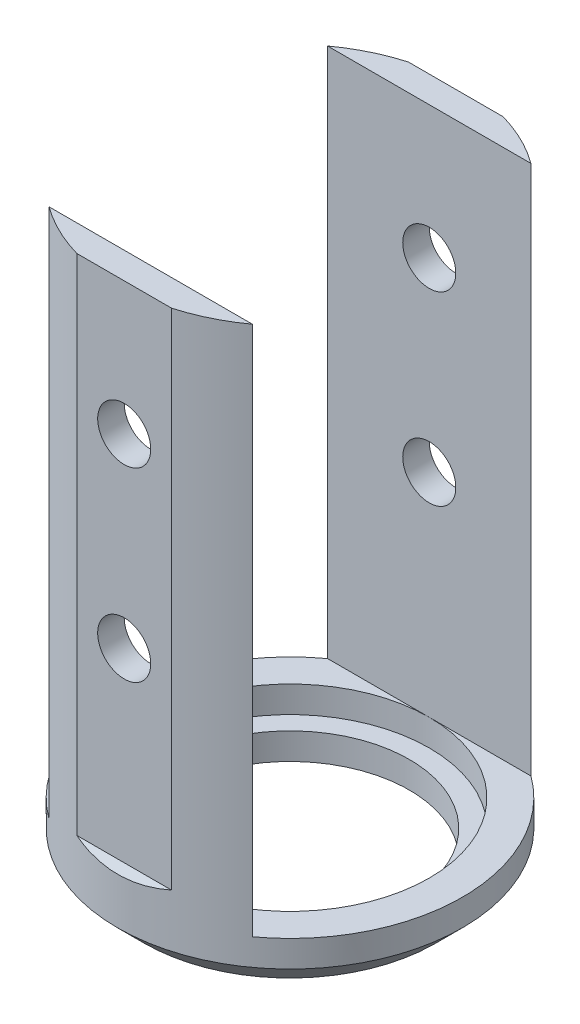
SolidWorks part; units mm, degrees
ref_plane "前视基准面" through (0, 0, 0) normal (0, 0, 1) x (1, 0, 0)
ref_plane "上视基准面" through (0, 0, 0) normal (0, 1, 0) x (1, 0, 0)
ref_plane "右视基准面" through (0, 0, 0) normal (1, 0, 0) x (0, 0, -1)
other "Configuration Table"
sketch "草图1" plane through (0, 0, 0) normal (0, 1, 0) x (1, 0, 0)
  circle A0 centre (0, 0) radius 4.5
  circle A1 centre (0, 0) radius 6.5
  dimension "D1" = 9
  dimension "D2" = 13
extrude "凸台-拉伸1" add sketch "草图1" along normal blind 2
sketch "草图2" plane through (0, 2, 0) normal (0, 1, 0) x (1, 0, 0)
  circle A0 centre (0, 0) radius 5.25
  dimension "D1" = 10.5
extrude "切除-拉伸1" cut sketch "草图2" against normal blind 1
sketch "草图3" plane through (0, 2, 0) normal (0, 1, 0) x (1, 0, 0)
  line L0 (-3.8324, 5.25) -> (3.8324, 5.25)
  line L1 (-3.8324, -5.25) -> (3.8324, -5.25)
  line L2 (-1.7854, 6.25) -> (1.7854, 6.25)
  line L3 (-1.7854, -6.25) -> (1.7854, -6.25)
  circle A0 centre (0, 0) radius 6.5
  circle A2 centre (0, 0) radius 6.5 construction
  circle A3 centre (0, 0) radius 5.25 construction
  circle M5 centre (0, 0) radius 6.5
  dimension "D1" = 1
  dimension "D2" = 1
extrude "凸台-拉伸2" add sketch "草图3" along normal blind 20 contours L0 M5 | L1 M5 region at (0, 2, -5.6943) region at (0, 2, 5.6943)
sketch "草图4" plane through (0, 0, 6.25) normal (0, 0, 1) x (1, 0, 0)
  line L0 (-1.7854, 2) -> (1.7854, 2) construction
  circle A0 centre (0, 17) radius 1
  circle A1 centre (0, 10) radius 1
  dimension "D1" = 2
  dimension "D2" = 15
  dimension "D3" = 8
extrude "切除-拉伸2" cut sketch "草图4" against normal blind 20
chamfer "倒角1" distance 1 angle 45 1 edges at (0, 0, 6.5)
chamfer "倒角2" distance 1 angle 45 2 edges at (0, 2, 6.25) (0, 2, -6.25)
sketch "草图5" plane through (0, 22, 0) normal (0, 1, 0) x (1, 0, 0)
  line L0 (-1.7854, -6.25) -> (1.7854, -6.25)
  line L1 (1.7854, -6.25) -> (2.6791, -7.0894)
  line L2 (2.6791, -7.0894) -> (-2.8605, -6.6772)
  line L3 (-2.8605, -6.6772) -> (-1.7854, -6.25)
